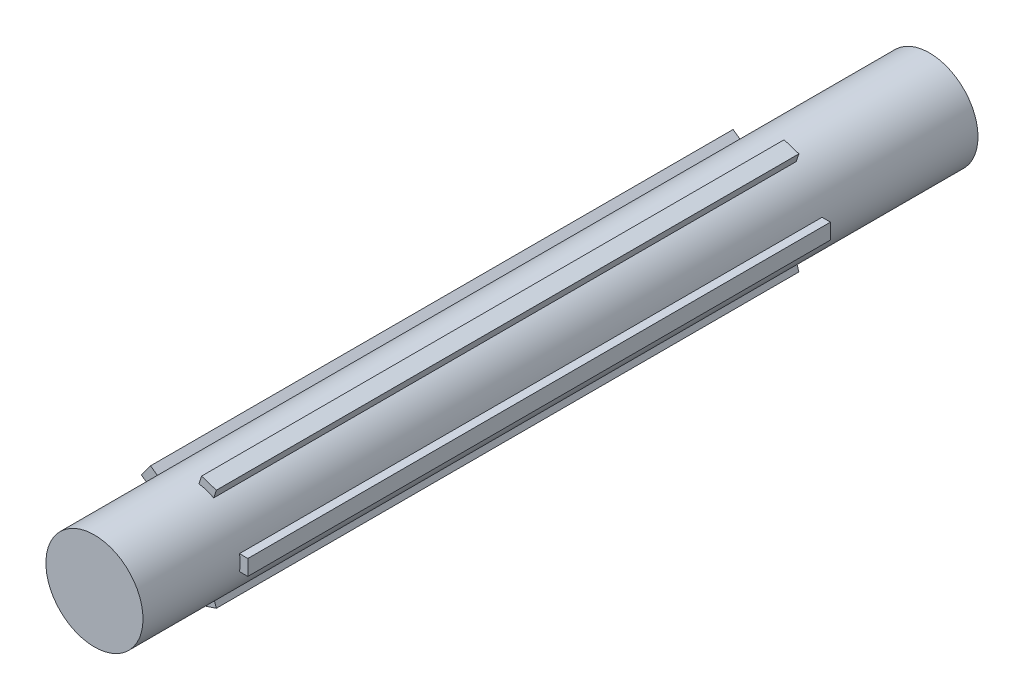
SolidWorks part; units mm, degrees
ref_plane "Front Plane" through (0, 0, 0) normal (0, 0, 1) x (1, 0, 0)
ref_plane "Top Plane" through (0, 0, 0) normal (0, 1, 0) x (1, 0, 0)
ref_plane "Right Plane" through (0, 0, 0) normal (1, 0, 0) x (0, 0, -1)
sketch "Sketch1" plane through (0, 0, 0) normal (0, 0, 1) x (1, 0, 0)
  line L1 (14.5, 2) -> (10.5, 2)
  line L2 (14.5, 2) -> (14.5, -2)
  line L3 (14.5, -2) -> (10.5, -2)
  line L4 (10.5, 2) -> (10.5, -2)
  line L5 (14.5, 2) -> (10.5, -2) construction
  line L6 (14.5, -2) -> (10.5, 2) construction
  circle A0 centre (0, 0) radius 12.5
  point P3 (12.5, 0)
  dimension "D1" = 4
  dimension "D3" = 25
  dimension "D2" = 4
extrude "Boss-Extrude1" add sketch "Sketch1" along normal blind 215 contours A0
extrude "Boss-Extrude2" add sketch "Sketch1<3>" along normal blind 150 from offset 40 contours A0 L3 L2 L1 | L4 L3 L2 L1 region at (13.4727, 0, 0)
sketch "Sketch1<3>" plane through (0, 0, 0) normal (0, 0, 1) x (1, 0, 0) same geometry as "Sketch1"
pattern_circular "CirPattern1" count 5 over 360 about axis through (0, 0, 215) along (0, 0, -1) of "Boss-Extrude2"
